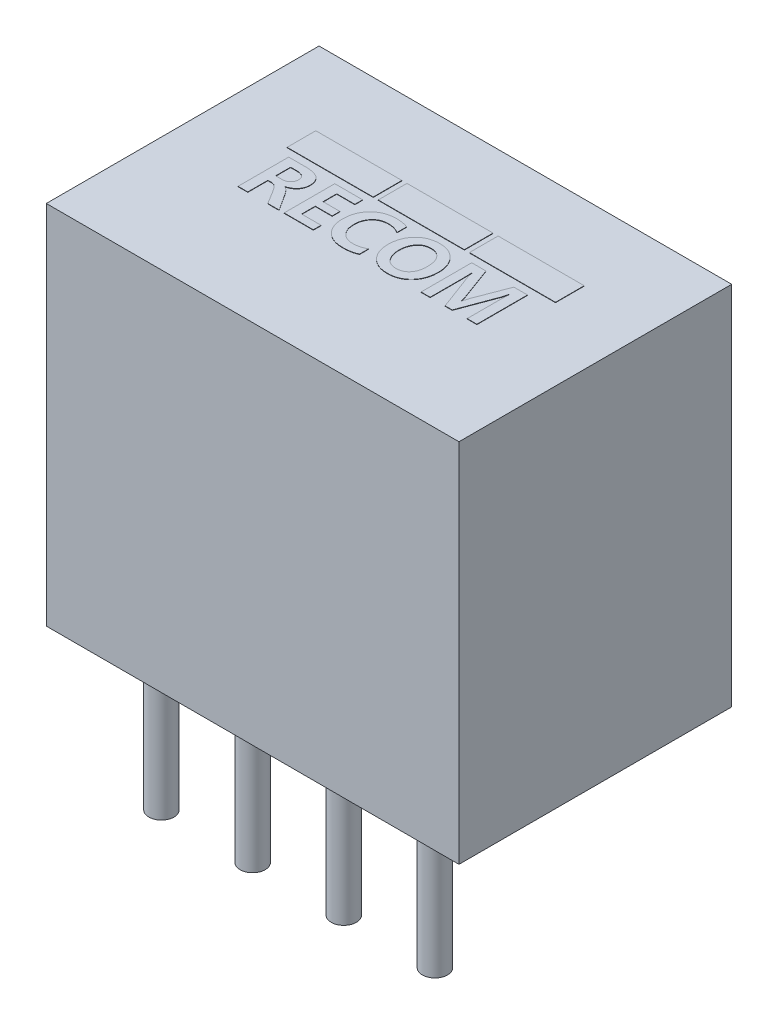
SolidWorks part; units mm, degrees
ref_plane "Front Plane" through (0, 0, 0) normal (0, 0, 1) x (1, 0, 0)
ref_plane "Top Plane" through (0, 0, 0) normal (0, 1, 0) x (1, 0, 0)
ref_plane "Right Plane" through (0, 0, 0) normal (1, 0, 0) x (0, 0, -1)
sketch "Sketch1" plane through (0, 0, 0) normal (0, 1, 0) x (1, 0, 0)
  line L0 (1.27, -1.2182) -> (1.27, -50000.2308) construction
  line L1 (-5.75, -3.8) -> (5.75, -3.8)
  line L2 (-5.75, -3.8) -> (-5.75, 3.8)
  line L3 (-5.75, 3.8) -> (5.75, 3.8)
  line L4 (5.75, -3.8) -> (5.75, 3.8)
  line L5 (-5.75, -3.8) -> (5.75, 3.8) construction
  line L6 (-5.75, 3.8) -> (5.75, -3.8) construction
  line L7 (-3.81, 1.0683) -> (-3.81, -49998.9317) construction
  line L8 (-1.27, -9.2663) -> (-1.27, 2.0854) construction
  line L9 (3.81, -9.3297) -> (3.81, -3.2594) construction
  line L10 (0, 0) -> (0, -6.7717) construction
  circle A0 centre (-1.27, -2.53) radius 0.35
  circle A1 centre (-3.81, -2.53) radius 0.35
  circle A2 centre (1.27, -2.53) radius 0.35
  circle A3 centre (3.81, -2.53) radius 0.35
  point P0 (0, 0)
  dimension "D3" = 0.7
  dimension "D1" = 11.5
  dimension "D2" = 7.6
  dimension "D4" = 1.27
  dimension "D5" = 2.54
  dimension "D6" = 2.54
  dimension "D7" = 2.54
  dimension "D8" = 1.27
extrude "Boss-Extrude1" add sketch "Sketch1" along normal blind 10.2 contours L1 L4 L3 L2 A2 A1 A0 | A0 | A2 | A1 | A3 region at (0, 0, -0.0454) region at (-1.27, 0, 2.53) region at (-3.81, 0, 2.53) region at (1.27, 0, 2.53) region at (3.81, 0, 2.53)
extrude "Boss-Extrude2" add sketch "Sketch1<3>" against normal blind 4.1 contours A2 | A0 | A1 | A3 region at (-1.27, 0, 2.53) region at (-3.81, 0, 2.53) region at (1.27, 0, 2.53)
sketch "Sketch1<3>" plane through (0, 0, 0) normal (0, 1, 0) x (1, 0, 0) same geometry as "Sketch1"
sketch "Sketch2" plane through (0, 10.2, 0) normal (0, 1, 0) x (1, 0, 0)
  line L0 (0, 7.4991) -> (0, -7.0772) construction
  line L1 (-3.74, 1.7) -> (-1.34, 1.7)
  line L2 (-3.74, 1.7) -> (-3.74, 0.9)
  line L3 (-3.74, 0.9) -> (-1.34, 0.9)
  line L4 (-1.34, 1.7) -> (-1.34, 0.9)
  line L5 (-3.74, 1.7) -> (-1.34, 0.9) construction
  line L6 (-3.74, 0.9) -> (-1.34, 1.7) construction
  line L7 (-1.2, 1.7) -> (1.2, 1.7)
  line L8 (-1.2, 1.7) -> (-1.2, 0.9)
  line L9 (-1.2, 0.9) -> (1.2, 0.9)
  line L10 (1.2, 1.7) -> (1.2, 0.9)
  line L11 (-1.2, 1.7) -> (1.2, 0.9) construction
  line L12 (-1.2, 0.9) -> (1.2, 1.7) construction
  line L13 (1.34, 1.7) -> (3.74, 1.7)
  line L14 (1.34, 1.7) -> (1.34, 0.9)
  line L15 (1.34, 0.9) -> (3.74, 0.9)
  line L16 (3.74, 1.7) -> (3.74, 0.9)
  line L17 (1.34, 1.7) -> (3.74, 0.9) construction
  line L18 (1.34, 0.9) -> (3.74, 1.7) construction
  line L19 (-2.54, 5.6376) -> (-2.54, 4.8793) construction
  line L20 (2.54, 7.0888) -> (2.54, -8.1777) construction
  line L21 (-5.75, -3.8) -> (5.75, -3.8) construction
  line L22 (-5.75, 3.8) -> (5.75, 3.8) construction
  text T0 "RECOM" font "@Malgun Gothic" height in points 5
  point P1 (-2.54, 1.3)
  point P6 (0, 1.3)
  point P11 (2.54, 1.3)
  point P24 (0, -3.8)
  point P25 (0, 0)
  point P26 (0, 0)
  point P27 (0, 0)
  point P30 (1.6332, 2.15)
  point P31 (0, 0)
  dimension "D1" = 2.54
  dimension "D2" = 2.54
  dimension "D3" = 0.8
  dimension "D4" = 2.5
  dimension "D5" = 2.4
extrude "Boss-Extrude3" add sketch "Sketch2" along normal blind 0.01
